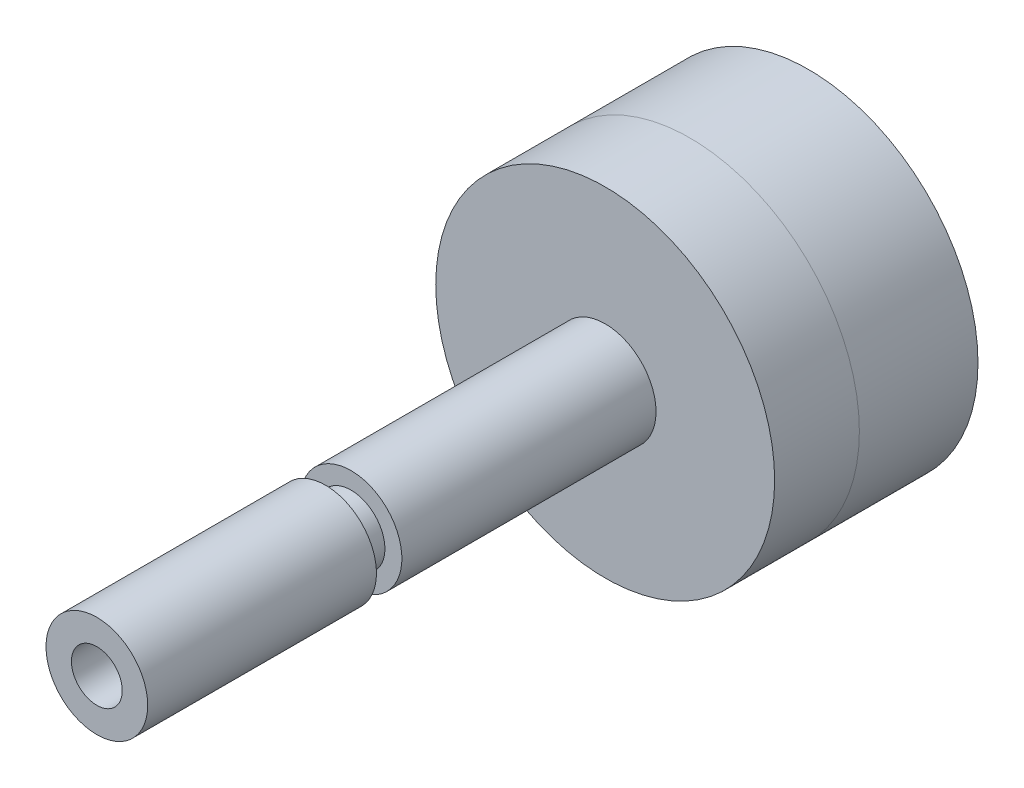
SolidWorks part; units mm, degrees
note: The reader was unsure of these and kept them because the rebuilt part matched: shared geometry of "Croquis1<6>", "Croquis1<7>".
ref_plane "Alzado" through (0, 0, 0) normal (0, 0, 1) x (1, 0, 0)
ref_plane "Planta" through (0, 0, 0) normal (0, 1, 0) x (1, 0, 0)
ref_plane "Vista lateral" through (0, 0, 0) normal (1, 0, 0) x (0, 0, -1)
sketch "Croquis1" plane through (0, 0, 0) normal (0, 0, 1) x (1, 0, 0)
  circle A0 centre (0, 0) radius 10
  circle A1 centre (0, 0) radius 3
  dimension "D1" = 20
  dimension "D2" = 6
extrude "Saliente-Extruir1" add sketch "Croquis1" along normal blind 5
extrude "Extruir-Lámina1" add sketch "Croquis1<6>" along normal blind 35 thin contours A1
sketch "Croquis1<6>" plane through (0, 0, 0) normal (0, 0, 1) x (1, 0, 0) same geometry as "Croquis1"
sketch "Croquis2" plane through (0, 0, 0) normal (0, 1, 0) x (1, 0, 0)
  line L0 (-3, -5) -> (-3, -35) construction
  line L1 (-3, -21.5) -> (-2, -21.5)
  line L2 (-3, -21.5) -> (-3, -20)
  line L3 (-3, -20) -> (-2, -20)
  line L4 (-2, -21.5) -> (-2, -20)
  line L5 (-3, -35) -> (3, -35) construction
  line L6 (0, 0) -> (0, -35) construction
  line L7 (10, 0) -> (-10, 0) construction
  dimension "D1" = 1
  dimension "D2" = 15
  dimension "D3" = 1.5
revolve "Cortar-Revolución2" cut sketch "Croquis2" angle 360 about L6
extrude "Extruir-Lámina2" add sketch "Croquis1<7>" against normal blind 7 separate body thin contours A0
sketch "Croquis1<7>" plane through (0, 0, 0) normal (0, 0, 1) x (1, 0, 0) same geometry as "Croquis1"
